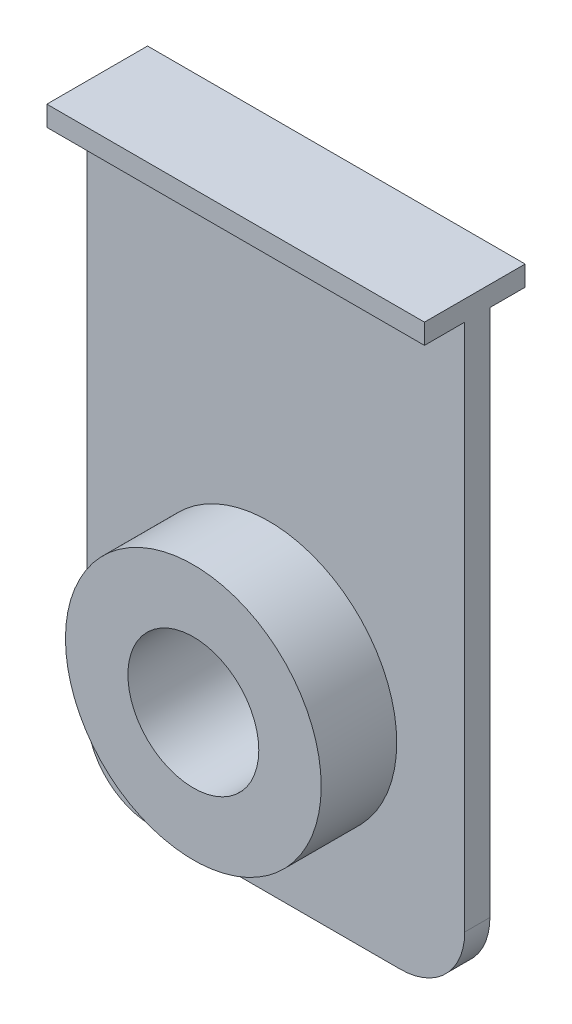
SolidWorks part; units mm, degrees
ref_plane "Front Plane" through (0, 0, 0) normal (0, 0, 1) x (1, 0, 0)
ref_plane "Top Plane" through (0, 0, 0) normal (0, 1, 0) x (1, 0, 0)
ref_plane "Right Plane" through (0, 0, 0) normal (1, 0, 0) x (0, 0, -1)
sketch "Sketch12" plane through (0, 0, 0) normal (0, 0, 1) x (1, 0, 0)
  line L0 (62.1258, 0) -> (62.1258, 121.71)
  line L1 (62.1258, 121.71) -> (137.1258, 121.71)
  line L2 (62.1258, 0) -> (137.1258, 0)
  line L3 (137.1258, 121.71) -> (137.1258, 0)
  circle A0 centre (99.6258, 37.5) radius 25.4
  circle A1 centre (99.6258, 37.5) radius 6.5
  dimension "D3" = 50.8
  dimension "D4" = 13
  dimension "D1" = 121.71
  dimension "D2" = 75
extrude "Boss-Extrude10" add sketch "Sketch12" along normal blind 5 separate body contours L1 L3 L2 L0
sketch "Sketch15" plane through (0, 0, 5) normal (0, 0, 1) x (1, 0, 0)
  circle A0 centre (98.2196, 38.6276) radius 25.4
  dimension "D1" = 50.8
extrude "Boss-Extrude11" add sketch "Sketch15" along normal blind 15
sketch "Sketch23" plane through (0, 0, 20) normal (0, 0, 1) x (1, 0, 0)
  circle A0 centre (98.2196, 38.6276) radius 13
  dimension "D1" = 26
extrude "Cut-Extrude7" cut sketch "Sketch23" against normal through all
sketch "Sketch24" plane through (0, 0, 5) normal (0, 0, 1) x (1, 0, 0)
  line L0 (62.1258, 121.71) -> (62.1258, 117.71)
  line L1 (62.1258, 0) -> (62.1258, 121.71) construction
  line L2 (62.1258, 117.71) -> (137.1258, 117.71)
  line L3 (137.1258, 121.71) -> (137.1258, 0) construction
  line L4 (137.1258, 117.71) -> (137.1258, 121.71)
  line L5 (137.1258, 121.71) -> (62.1258, 121.71)
  dimension "D1" = 4
extrude "Boss-Extrude13" add sketch "Sketch24" along normal blind 8 and the other way blind 12
fillet "Fillet2" radius 12.8 2 edges at (137.1258, 0, 2.5) (62.1258, 0, 2.5)
